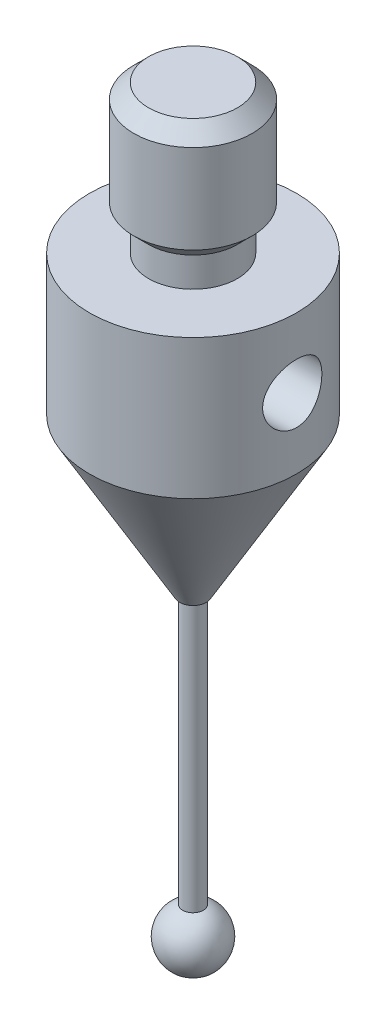
SolidWorks part; units mm, degrees
ref_plane "Front Plane" through (0, 0, 0) normal (0, 0, 1) x (1, 0, 0)
ref_plane "Top Plane" through (0, 0, 0) normal (0, 1, 0) x (1, 0, 0)
ref_plane "Right Plane" through (0, 0, 0) normal (1, 0, 0) x (0, 0, -1)
sketch "Sketch1" plane through (0, 0, 0) normal (0, 0, 1) x (1, 0, 0)
  line L0 (0, 0) -> (0, -1)
  line L1 (0, 0) -> (0, 1)
  arc A0 (0, 1) -> (0, -1) centre (0, 0) cw
  dimension "D1" = 2
revolve "Revolve1" add sketch "Sketch1" angle 360 about L1
sketch "Sketch2" plane through (0, 0, 0) normal (0, 1, 0) x (1, 0, 0)
  circle A1 centre (0, 0) radius 0.35
  dimension "D2" = 0.7
extrude "Boss-Extrude2" add sketch "Sketch2" along normal blind 10 contours A1
sketch "Sketch4" plane through (0, 10, 0) normal (0, 1, 0) x (1, 0, 0)
  circle A0 centre (0, 0) radius 3.5
  dimension "D1" = 7
extrude "Boss-Extrude3" add sketch "Sketch4" along normal blind 10
chamfer "Chamfer1" distance 3.05 angle 60 1 edges at (0, 10, 3.5) first distance on face at (0, 10, 0.35)
sketch "Sketch5" plane through (0, 0, 0) normal (1, 0, 0) x (0, 0, -1)
  line L0 (0, 20) -> (0, 15.2828) construction
  line L1 (3.5, 20) -> (-3.5, 20) construction
  line L2 (-3.5, 15.2828) -> (3.5, 15.2828) construction
  circle A0 centre (0, 17.6414) radius 1
  dimension "D1" = 2
extrude "Cut-Extrude4" cut sketch "Sketch5" against normal through all both and the other way through all
sketch "Sketch6" plane through (0, 20, 0) normal (0, 1, 0) x (1, 0, 0)
  circle A0 centre (0, 0) radius 1.5
  dimension "D1" = 3
extrude "Boss-Extrude4" add sketch "Sketch6" along normal blind 1
sketch "Sketch7" plane through (0, 21, 0) normal (0, 1, 0) x (1, 0, 0)
  circle A0 centre (0, 0) radius 2
  dimension "D1" = 4
extrude "Boss-Extrude5" add sketch "Sketch7" along normal blind 4
chamfer "Chamfer2" distance 0.5 angle 45 2 edges at (0, 25, 2) (0, 21, 2)
